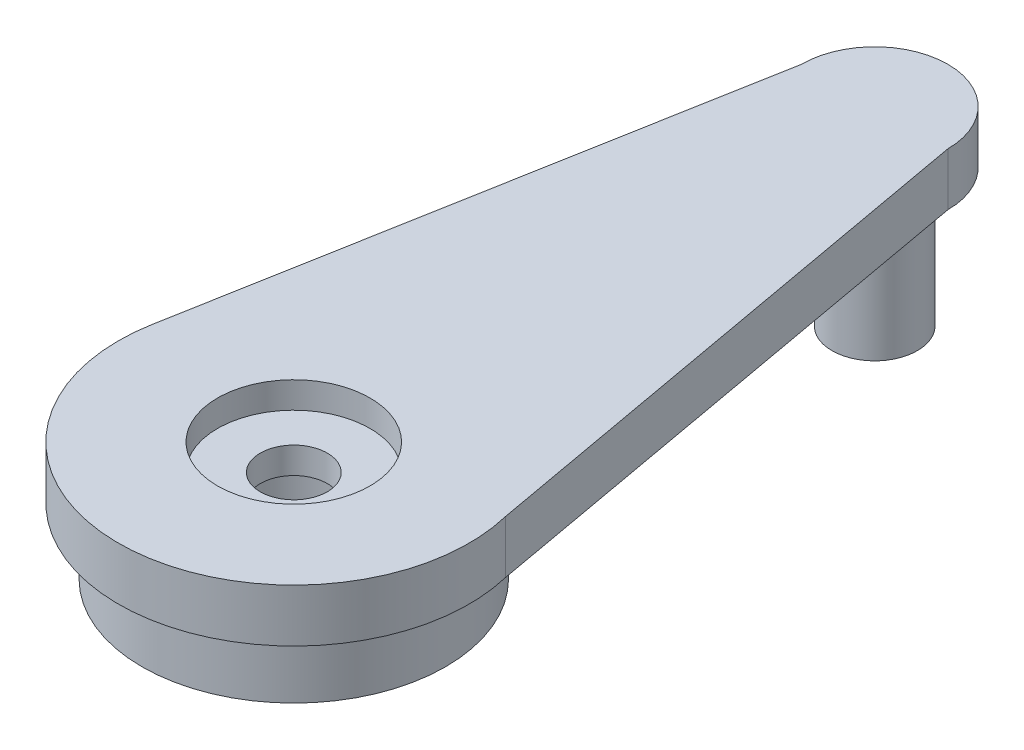
SolidWorks part; units mm, degrees
ref_plane "Front Plane" through (0, 0, 0) normal (0, 0, 1) x (1, 0, 0)
ref_plane "Top Plane" through (0, 0, 0) normal (0, 1, 0) x (1, 0, 0)
ref_plane "Right Plane" through (0, 0, 0) normal (1, 0, 0) x (0, 0, -1)
sketch "Sketch1" plane through (0, 0, 0) normal (0, 1, 0) x (1, 0, 0)
  line L0 (39.6969, -14.5469) -> (35.9359, -35.3665)
  line L1 (45.2401, -14.5469) -> (49.0636, -35.757)
  circle A5 centre (42.4685, -14.5469) radius 1.6168
  circle A6 centre (42.4704, -36.5469) radius 2.8871
  circle A7 centre (42.4704, -36.5469) radius 6.6403
  circle A8 centre (42.4685, -14.5469) radius 2.7716
  circle A9 centre (42.4704, -36.5469) radius 1.2703
  dimension "D1" = 22
extrude "Boss-Extrude1" add sketch "Sketch1" along normal blind 2 contours A8 L0 A7 L1 | A8 A5 | A5 | A9 | A6 A9 | A7 region at (42.4644, 0, 24.5412) region at (42.4685, 0, 11.8537) region at (42.4685, 0, 14.5469) region at (39.665, 0, 36.5469) region at (42.4704, 0, 36.5469)
extrude "Boss-Extrude2" add sketch "Sketch1<4>" along normal blind 1 contours A6 A9 region at (39.665, 0, 36.5469)
sketch "Sketch1<4>" plane through (0, 0, 0) normal (0, 1, 0) x (1, 0, 0) same geometry as "Sketch1"
extrude "Boss-Extrude5" add sketch "Sketch1<6>" against normal blind 5.2 contours A5 region at (42.4685, 0, 14.5469)
sketch "Sketch1<6>" plane through (0, 0, 0) normal (0, 1, 0) x (1, 0, 0) same geometry as "Sketch1"
sketch "Sketch3" plane through (0, 0, 0) normal (0, -1, 0) x (1, 0, 0)
  circle A0 centre (42.4704, 36.5469) radius 1.1
  circle A1 centre (42.4704, 36.5469) radius 5.75
  circle A2 centre (42.4704, 36.5469) radius 2.5
  arc M6 (48.9244, 34.9848) -> (35.9359, 35.3665) centre (42.4704, 36.5469) ccw
extrude "Boss-Extrude6" add sketch "Sketch3" along normal blind 2.5 contours A1 A2 M6 region at (36.883, 0, 36.5469)
